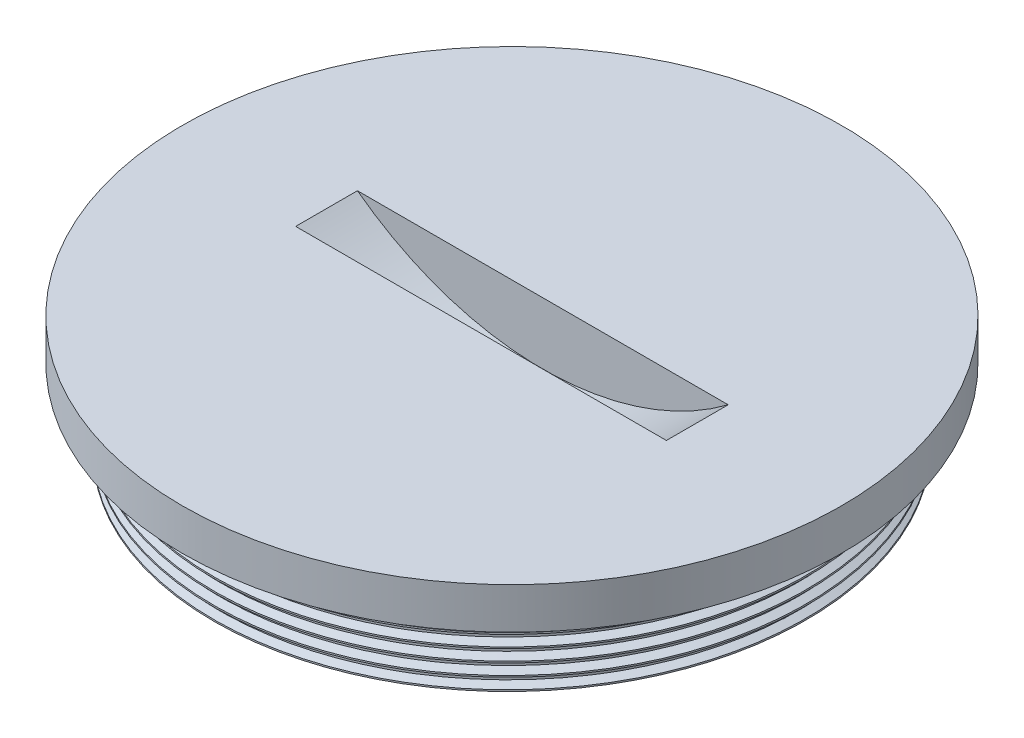
SolidWorks part; units mm, degrees
ref_plane "Front Plane" through (0, 0, 0) normal (0, 0, 1) x (1, 0, 0)
ref_plane "Top Plane" through (0, 0, 0) normal (0, 1, 0) x (1, 0, 0)
ref_plane "Right Plane" through (0, 0, 0) normal (1, 0, 0) x (0, 0, -1)
sketch "Sketch1" plane through (0, 0, 0) normal (0, 1, 0) x (1, 0, 0)
  circle A0 centre (0, 0) radius 14.05
  dimension "D1" = 28.1
extrude "Boss-Extrude1" add sketch "Sketch1" along normal blind 12.7
thread "MinColWidth_OnTracking1" pitch 0.6 method extrude profile "HeaderRowsCount1" start angle 0, offset 0, length 12.7, pitch 0.6, diameter 28.1
ref_plane "Plane1" through (-14.05, 12.7, 0) normal (0, 0, 1) x (-1, 0, 0)
sketch "HeaderRowsCount1" plane through (-14.05, 12.7, 0) normal (0, 0, 1) x (-1, 0, 0)
  line L0 (0, 0) -> (0, 0.6) construction
  line L1 (0, 0) -> (0.3248, 0.1875)
  line L2 (0.3248, 0.1875) -> (0.3248, 0.2625)
  line L3 (0.3248, 0.2625) -> (0, 0.45)
  line L4 (0.3248, 0.225) -> (0, 0.225) construction
  line L11 (0, 0) -> (0, 0.45)
  point P2 (0, 0)
  dimension "Pitch" = 0.6
  dimension "Profile_Angle" = 60
  dimension "Profile_Land" = 0.075
  dimension "Profile_Height" = 0.3248
sketch "Sketch2" plane through (0, 0, 0) normal (0, 0, 1) x (1, 0, 0)
  line L0 (0, 0) -> (0, 19.0669) construction
  line L1 (-25, 7.905) -> (25, 7.905)
  line L2 (-25, 7.905) -> (-25, 4.095)
  line L3 (-25, 4.095) -> (25, 4.095)
  line L4 (25, 7.905) -> (25, 4.095)
  line L5 (-25, 7.905) -> (25, 4.095) construction
  line L6 (-25, 4.095) -> (25, 7.905) construction
  point P0 (0, 6)
  dimension "D1" = 50
  dimension "D2" = 3.81
  dimension "D3" = 6
extrude "Cut-Extrude2" cut sketch "Sketch2" against normal through all both and the other way through all flip side to cut
sketch "Sketch3" plane through (0, 7.905, 0) normal (0, 1, 0) x (1, 0, 0)
  circle A0 centre (0, 0) radius 16
  dimension "D1" = 32
extrude "Boss-Extrude2" add sketch "Sketch3" along normal blind 2
sketch "Sketch4" plane through (0, 0, 0) normal (0, 0, 1) x (1, 0, 0)
  line L0 (16, 9.905) -> (-16, 9.905) construction
  line L1 (-9, 9.905) -> (9, 9.905)
  arc A0 (-9, 9.905) -> (9, 9.905) centre (0, 21.905) ccw
  dimension "D1" = 15
  dimension "D2" = 12
extrude "Cut-Extrude3" cut sketch "Sketch4" against normal blind 1.5 and the other way blind 1.5
